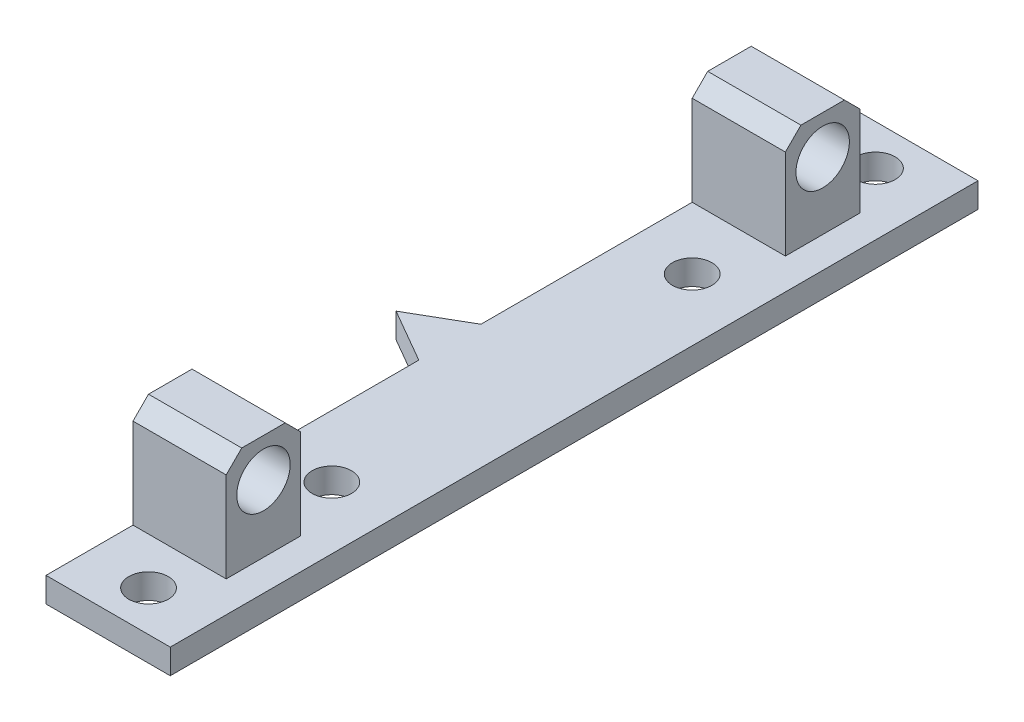
SolidWorks part; units mm, degrees
ref_plane "Front Plane" through (0, 0, 0) normal (0, 0, 1) x (1, 0, 0)
ref_plane "Top Plane" through (0, 0, 0) normal (0, 1, 0) x (1, 0, 0)
ref_plane "Right Plane" through (0, 0, 0) normal (1, 0, 0) x (0, 0, -1)
sketch "Sketch1" plane through (0, 0, 0) normal (0, 1, 0) x (1, 0, 0)
  line L1 (0, 0) -> (20, 0)
  line L2 (0, 0) -> (0, 130)
  line L3 (0, 130) -> (20, 130)
  line L4 (20, 0) -> (20, 130)
  dimension "D1" = 130
  dimension "D2" = 20
extrude "Boss-Extrude1" add sketch "Sketch1" along normal blind 4
sketch "Sketch2" plane through (0, 0, 0) normal (-1, 0, 0) x (0, 0, 1)
  line L0 (-130, 0) -> (0, 0) construction
  line L5 (-14, 18.5) -> (-16.5, 21)
  line L6 (-116, 0) -> (-104, 0)
  line L7 (-116, 0) -> (-116, 21)
  line L8 (-116, 21) -> (-104, 21)
  line L9 (-104, 0) -> (-104, 21)
  line L10 (-130, 0) -> (-116, 0) construction
  line L11 (-106.5, 21) -> (-104, 18.5)
  line L12 (-116, 18.5) -> (-113.5, 21)
  line L13 (-65, 0) -> (-65, 4) construction
  line L14 (-23.5, 21) -> (-26, 18.5)
  line L15 (-130, 4) -> (0, 4) construction
  line L16 (-26, 0) -> (-26, 21)
  line L17 (-14, 21) -> (-26, 21)
  line L18 (-14, 0) -> (-14, 21)
  line L19 (-14, 0) -> (-26, 0)
  circle A0 centre (-110, 14.8) radius 4.3
  circle A1 centre (-20, 14.8) radius 4.3
  point P10 (-110, 21)
  point P25 (-65, 4)
  point P30 (-20, 21)
  line M15 (0, 4) -> (-130, 4)
  dimension "D4" = 8.6
  dimension "D2" = 12
  dimension "D3" = 21
  dimension "D5" = 14.8
  dimension "D6" = 2.5
  dimension "D7" = 2.5
  dimension "D8" = 2.5
  dimension "D9" = 2.5
  dimension "D1" = 90
extrude "Boss-Extrude2" add sketch "Sketch2" against normal blind 15 contours L18 L5 L17 L14 L16 A1 M15 | L12 L7 L9 L11 L8 A0 M15 region at (0, 11.25, -14.2081) region at (0, 4.2081, -110)
sketch "Sketch3" plane through (0, 0, 0) normal (0, -1, 0) x (1, 0, 0)
  line L0 (0, -70) -> (-8.6603, -65)
  line L1 (0, -130) -> (0, 0) construction
  line L2 (-8.6603, -65) -> (0, -60)
  line L3 (0, -70) -> (0, -60)
  point P6 (0, -65)
  dimension "D1" = 10
  dimension "D2" = 10
  dimension "D3" = 10
extrude "Boss-Extrude3" add sketch "Sketch3" against normal up to surface (4 mm away) up to face at (8.3333, 4, -65)
sketch "Sketch4" plane through (0, 4, 0) normal (0, 1, 0) x (1, 0, 0)
  line L0 (10, 130) -> (10, 0) construction
  line L1 (20, 130) -> (0, 130) construction
  line L2 (0, 0) -> (20, 0) construction
  circle A0 centre (10, 123.5) radius 3.175
  circle A1 centre (10, 94) radius 3.175
  circle A2 centre (10, 36) radius 3.175
  circle A3 centre (10, 6.5) radius 3.175
  dimension "D1" = 6.35
  dimension "D2" = 6.5
  dimension "D3" = 36
  dimension "D4" = 6.5
  dimension "D5" = 36
extrude "Cut-Extrude1" cut sketch "Sketch4" against normal through all
equation "\"8mm hole\" = 8.6mm"
equation "\"D4@Sketch2\"= \"8mm hole\""
